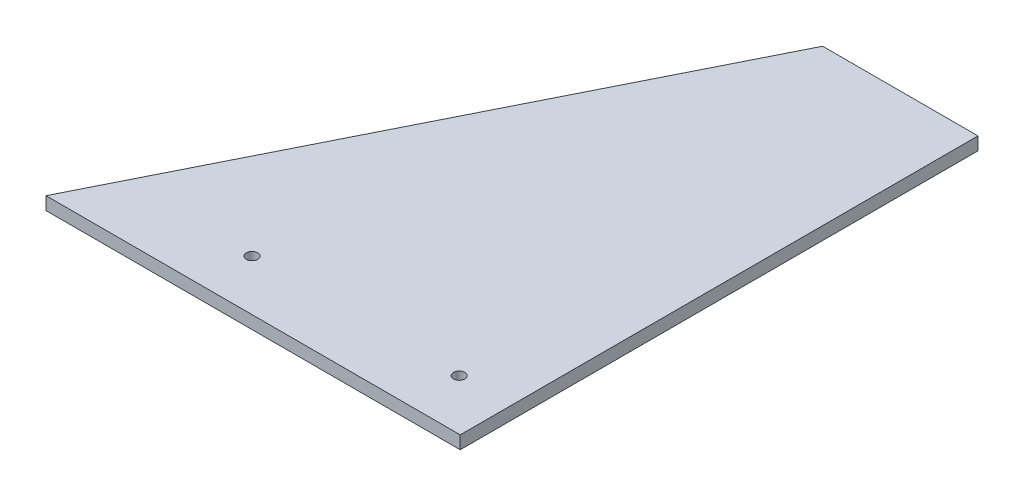
SolidWorks part; units mm, degrees
material "Balsa"
ref_plane "Front Plane" through (0, 0, 0) normal (0, 0, 1) x (1, 0, 0)
ref_plane "Top Plane" through (0, 0, 0) normal (0, 1, 0) x (1, 0, 0)
ref_plane "Right Plane" through (0, 0, 0) normal (1, 0, 0) x (0, 0, -1)
sketch "Sketch1" plane through (0, 0, 0) normal (0, 1, 0) x (1, 0, 0)
  line L0 (0, 0) -> (0, 127)
  line L1 (0, 127) -> (-38.1, 127)
  line L2 (-38.1, 127) -> (-101.6, 0)
  line L3 (-101.6, 0) -> (0, 0)
  dimension "D1" = 101.6
  dimension "D2" = 127
  dimension "D3" = 38.1
extrude "Boss-Extrude1" add sketch "Sketch1" along normal blind 3.175
sketch "Sketch2" plane through (0, 0, 0) normal (0, -1, 0) x (-1, 0, 0)
  line L0 (101.6, 0) -> (0, 0) construction
  line L1 (0, 0) -> (0, 127) construction
  circle A0 centre (63.5, 12.446) radius 1.397
  circle A1 centre (12.7, 12.446) radius 1.397
  point P8 (0, 0)
  dimension "D1" = 2.794
  dimension "D2" = 2.794
  dimension "D3" = 12.446
  dimension "D5" = 50.8
  dimension "D4" = 12.7
extrude "Cut-Extrude1" cut sketch "Sketch2" against normal blind 12.7
